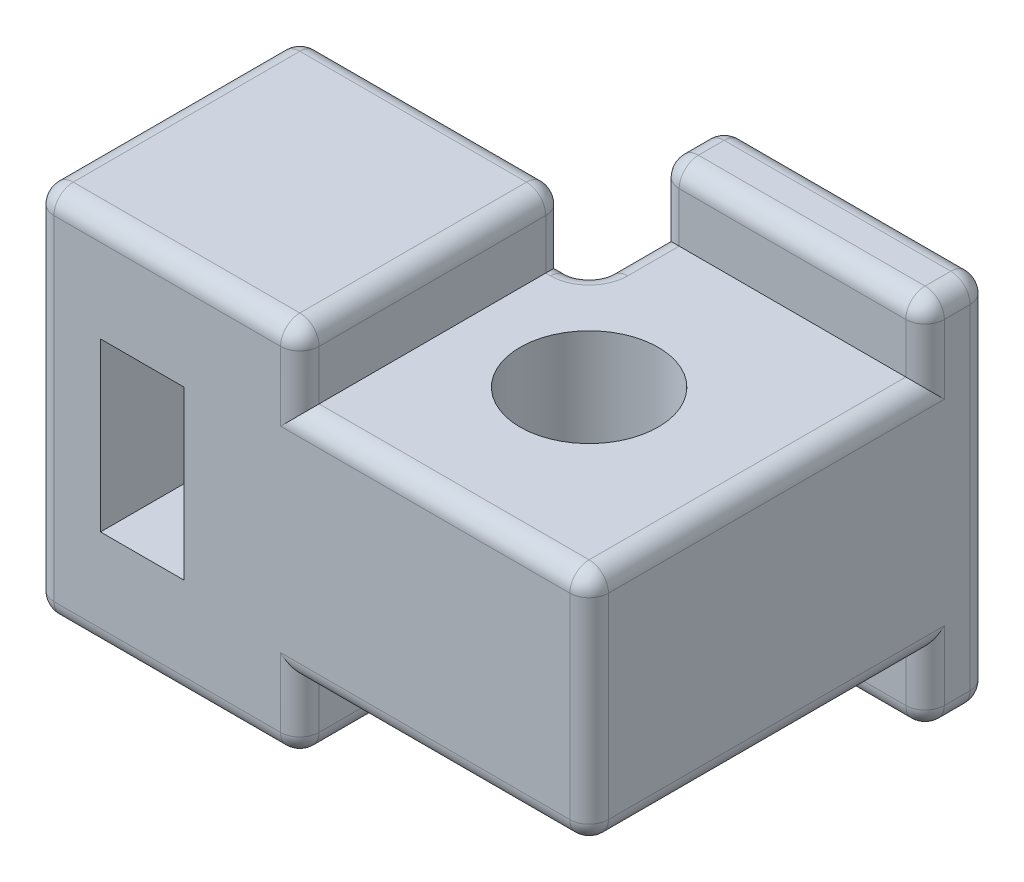
SolidWorks part; units mm, degrees
ref_plane "Front" through (0, 0, 0) normal (0, 0, 1) x (1, 0, 0)
ref_plane "Top" through (0, 0, 0) normal (0, 1, 0) x (1, 0, 0)
ref_plane "Right" through (0, 0, 0) normal (1, 0, 0) x (0, 0, -1)
sketch "Sketch1" plane through (0, 0, 0) normal (0, 1, 0) x (1, 0, 0)
  line L0 (-11.1125, 3.81) -> (-3.81, 3.81)
  line L1 (-3.81, 3.81) -> (-3.81, 9.144)
  line L2 (-3.81, 9.144) -> (6.6675, 9.144)
  line L3 (6.6675, 9.144) -> (6.6675, -6.6675)
  line L4 (6.6675, -6.6675) -> (-11.1125, -6.6675)
  line L5 (-11.1125, -6.6675) -> (-11.1125, 3.81)
  line L7 (0, 9.144) -> (0, 0) construction
  line L8 (-11.1125, 0) -> (0, 0) construction
  circle A0 centre (0, 0) radius 2.7305
  dimension "D1" = 5.461
  dimension "D2" = 10.4775
  dimension "D3" = 11.1125
  dimension "D4" = 9.144
  dimension "D5" = 5.334
  dimension "D6" = 17.78
extrude "Boss-Extrude1" add sketch "Sketch1" along normal mid plane 9.271
sketch "Sketch2" plane through (-11.1125, 0, 0) normal (-1, 0, 0) x (0, 0, 1)
  line L1 (-3.81, 4.6355) -> (6.6675, 4.6355)
  line L2 (-3.81, 4.6355) -> (-3.81, -4.6355)
  line L3 (-3.81, -4.6355) -> (6.6675, -4.6355)
  line L4 (6.6675, 4.6355) -> (6.6675, -4.6355)
extrude "Boss-Extrude2" add sketch "Sketch2" along normal blind 4.1275
sketch "Sketch3" plane through (0, 0, 0) normal (0, 1, 0) x (1, 0, 0)
  line L0 (6.6675, 9.144) -> (6.6675, -6.6675) construction
  line L1 (6.6675, 6.604) -> (-3.81, 6.604)
  line L2 (6.6675, 6.604) -> (6.6675, 9.144)
  line L3 (6.6675, 9.144) -> (-3.81, 9.144)
  line L4 (-3.81, 6.604) -> (-3.81, 9.144)
  line L5 (-3.81, 9.144) -> (6.6675, 9.144) construction
  line L6 (-3.81, 3.81) -> (-3.81, 9.144) construction
  line L8 (-4.7625, -6.6675) -> (-15.24, -6.6675)
  line L9 (-4.7625, -6.6675) -> (-4.7625, 3.81)
  line L10 (-4.7625, 3.81) -> (-15.24, 3.81)
  line L11 (-15.24, -6.6675) -> (-15.24, 3.81)
  line L12 (-15.24, -6.6675) -> (-15.24, 3.81) construction
  line L13 (6.6675, -6.6675) -> (-11.1125, -6.6675) construction
  line L14 (-11.1125, 3.81) -> (-3.81, 3.81) construction
  line L15 (0, 9.144) -> (0, 0) construction
  circle A0 centre (0, 0) radius 2.7305 construction
  dimension "D1" = 6.604
  dimension "D2" = 4.7625
extrude "Boss-Extrude3" add sketch "Sketch3" along normal mid plane 14.732
sketch "Sketch4" plane through (0, 0, -3.81) normal (0, 0, -1) x (-1, 0, 0)
  line L0 (6.731, 0) -> (15.24, 0) construction
  line L1 (9.3345, 3.302) -> (12.6365, 3.302)
  line L2 (9.3345, 3.302) -> (9.3345, -3.302)
  line L3 (9.3345, -3.302) -> (12.6365, -3.302)
  line L4 (12.6365, 3.302) -> (12.6365, -3.302)
  line L5 (15.24, 7.366) -> (15.24, -7.366) construction
  line L6 (3.81, 4.6355) -> (3.81, -4.6355) construction
  line L7 (10.9855, 3.302) -> (10.9855, -3.302) construction
  point P12 (10.9855, 0)
  dimension "D1" = 3.302
  dimension "D2" = 6.604
  dimension "D3" = 7.1755
extrude "Cut-Extrude1" cut sketch "Sketch4" against normal up to surface (10.4775 mm away) up to face at (-4.5244, 0, 6.6675)
fillet "Fillet1" radius 0.762 38 edges at (-10.0012, 7.366, 6.6675) (-10.0012, 7.366, -3.81) (6.6675, 7.366, -7.874) (-3.81, 7.366, -7.874) (1.4288, 7.366, -9.144) (-15.24, 7.366, 1.4288) (-15.24, 0, 6.6675) (-15.24, 0, -3.81) (-3.81, 0, -9.144) (6.6675, 0, -9.144) (-10.0012, -7.366, 6.6675) (-15.24, -7.366, 1.4288) (-10.0012, -7.366, -3.81) (-3.81, -7.366, -7.874) (1.4288, -7.366, -9.144) (6.6675, -7.366, -7.874) (6.6675, 0, 6.6675) (6.6675, -4.6355, 0.0317) (0.9525, -4.6355, 6.6675) (6.6675, 4.6355, 0.0317) (0.9525, 4.6355, 6.6675) (-4.2862, -4.6355, -3.81) (-3.81, -4.6355, -5.207) (-4.2862, 4.6355, -3.81) (-3.81, 4.6355, -5.207) (-4.7625, 7.366, 1.4287) (1.4288, 7.366, -6.604) (6.6675, 6.0008, -6.604) (-4.7625, 6.0008, 6.6675) (-4.7625, -6.0008, 6.6675) (6.6675, -6.0008, -6.604) (-3.81, 6.0008, -6.604) (-4.7625, 6.0008, -3.81) (1.4288, -7.366, -6.604) (-3.81, -6.0008, -6.604) (-4.7625, -7.366, 1.4287) (-4.7625, -6.0008, -3.81) (-3.81, 0, -3.81)
